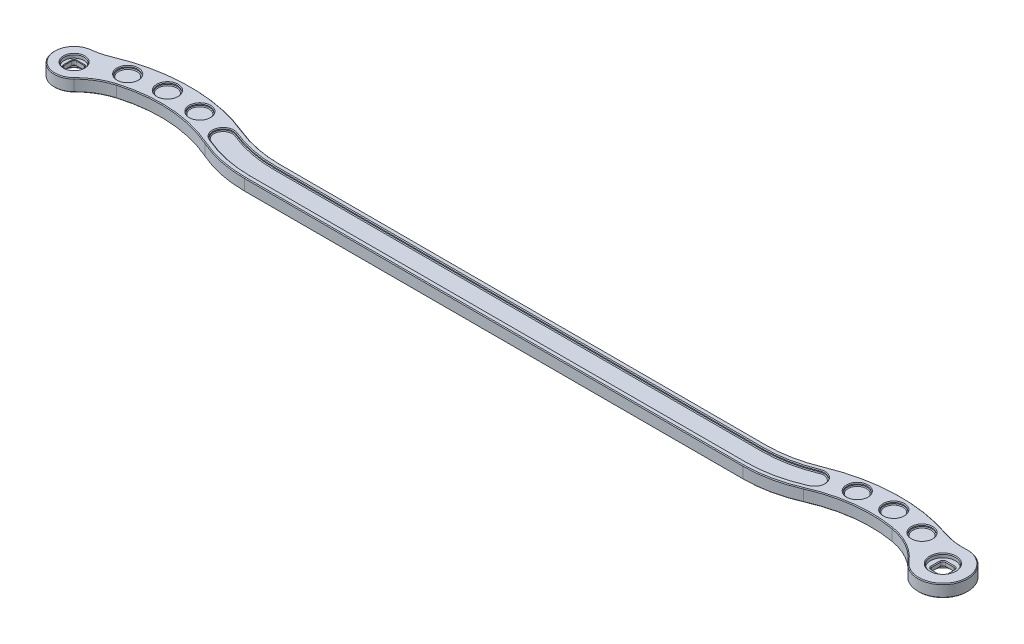
SolidWorks part; units mm, degrees
material "보통 탄소강"
ref_plane "정면" through (0, 0, 0) normal (0, 0, 1) x (1, 0, 0)
ref_plane "윗면" through (0, 0, 0) normal (0, 1, 0) x (1, 0, 0)
ref_plane "우측면" through (0, 0, 0) normal (1, 0, 0) x (0, 0, -1)
sketch "스케치1" plane through (0, 0, 0) normal (0, 1, 0) x (1, 0, 0)
  line L0 (0, 0) -> (350, 0) construction
  line L1 (77.0777, 6) -> (272.9223, 6)
  line L2 (74.6146, -6) -> (275.3854, -6)
  line L3 (335, 6.5992) -> (318, -52.3889) construction
  line L4 (75.0349, -4) -> (274.9651, -4)
  line L5 (0, 0) -> (32, 0) construction
  line L6 (32, 3) -> (32, 15) construction
  line L7 (32, 3) -> (32, 9) construction
  line L8 (175, 6) -> (175, -6) construction
  line L9 (273.3234, 4) -> (76.6766, 4)
  line L10 (307.4208, 8.0816) -> (318, -52.3889) construction
  line L11 (321.2949, 8.9115) -> (318, -52.3889) construction
  line L12 (294.089, 4.1521) -> (318, -52.3889) construction
  line L14 (347.25, -2.75) -> (352.75, -2.75)
  line L15 (347.25, -2.75) -> (347.25, 2.75)
  line L16 (347.25, 2.75) -> (352.75, 2.75)
  line L17 (352.75, -2.75) -> (352.75, 2.75)
  line L18 (347.25, -2.75) -> (352.75, 2.75) construction
  line L19 (347.25, 2.75) -> (352.75, -2.75) construction
  line L20 (2.5, -2.5) -> (-2.5, -2.5)
  line L21 (2.5, -2.5) -> (2.5, 2.5)
  line L22 (2.5, 2.5) -> (-2.5, 2.5)
  line L23 (-2.5, -2.5) -> (-2.5, 2.5)
  line L24 (2.5, -2.5) -> (-2.5, 2.5) construction
  line L25 (2.5, 2.5) -> (-2.5, -2.5) construction
  circle A2 centre (0, 0) radius 8
  circle A3 centre (350, 0) radius 10
  circle A6 centre (350, 0) radius 5
  circle A9 centre (32, 0) radius 3
  arc A11 (72.1368, -5.9386) -> (-6.5409, -4.6061) centre (32, -52.3889) ccw
  arc A12 (54.3968, -1.7301) -> (16.393, 0.7557) centre (32, -52.3889) ccw
  arc A13 (57.8775, 9.8334) -> (5.8839, 9.7336) centre (32, -52.3889) ccw
  arc A14 (57.3175, 7.8999) -> (13.8923, 10.4428) centre (32, -52.3889) ccw
  arc A15 (54.9979, 0.1904) -> (16.1077, 2.7556) centre (32, -52.3889) ccw
  circle A16 centre (15, 6.5992) radius 4
  circle A17 centre (32, -52.3889) radius 67.3889 construction
  circle A18 centre (32, -52.3889) radius 65.3889 construction
  circle A19 centre (32, -52.3889) radius 57.3889 construction
  circle A20 centre (32, -52.3889) radius 55.3889 construction
  arc A21 (64, 0) -> (18.8776, 7.5811) centre (32, -52.3889) ccw
  arc A22 (77.0777, 6) -> (57.8775, 9.8334) centre (77.0777, 56) cw
  arc A23 (76.6766, 4) -> (57.3175, 7.8999) centre (76.6766, 54) cw
  arc A24 (54.3968, -1.7301) -> (74.6146, -6) centre (74.6146, 44) ccw
  arc A25 (75.0349, -4) -> (54.9979, 0.1904) centre (75.0349, 46) cw
  arc A27 (295.0021, 0.1904) -> (333.8923, 2.7556) centre (318, -52.3889) cw
  arc A28 (274.9651, -4) -> (295.0021, 0.1904) centre (274.9651, 46) ccw
  arc A29 (295.6032, -1.7301) -> (275.3854, -6) centre (275.3854, 44) cw
  arc A30 (272.9223, 6) -> (292.1225, 9.8334) centre (272.9223, 56) ccw
  arc A31 (273.3234, 4) -> (292.6825, 7.8999) centre (273.3234, 54) ccw
  circle A32 centre (335, 6.5992) radius 4
  arc A33 (292.6825, 7.8999) -> (336.1077, 10.4428) centre (318, -52.3889) cw
  arc A34 (292.1225, 9.8334) -> (339.9749, 11.3164) centre (318, -52.3889) cw
  arc A35 (295.6032, -1.7301) -> (327.3652, 2.2025) centre (318, -52.3889) cw
  arc A36 (339.9749, 11.3164) -> (349.4649, 9.9857) centre (348.1272, 34.9499) ccw
  arc A37 (342.3252, -6.4107) -> (327.3652, 2.2025) centre (323.1382, -22.4375) ccw
  circle A38 centre (321.2949, 8.9115) radius 4
  circle A39 centre (307.4208, 8.0816) radius 4
  circle A40 centre (294.089, 4.1521) radius 4.0002
  circle A42 centre (15, 6.5992) radius 4
  circle A43 centre (28.7051, 8.9115) radius 4
  circle A44 centre (42.5792, 8.0816) radius 4
  circle A45 centre (55.911, 4.1521) radius 4.0002
  arc A46 (-0.9224, 7.9467) -> (5.8839, 9.7336) centre (-3.8047, 32.7799) ccw
  arc A47 (16.393, 0.7557) -> (5.6818, -5.6318) centre (23.4373, -23.2313) ccw
  circle A48 centre (0, 0) radius 4
  point P53 (175, 0)
  point P54 (175, 0)
  dimension "D3" = 5.5
  dimension "D4" = 16
  dimension "D5" = 20
  dimension "D8" = 4
  dimension "D11" = 10
  dimension "D12" = 50
  dimension "D14" = 6
  dimension "D9" = 2
  dimension "D18" = 50
  dimension "D19" = 13
  dimension "D21" = 13
  dimension "D22" = 8
  dimension "D23" = 50
  dimension "D24" = 25
  dimension "D27" = 8
  dimension "D1" = 350
  dimension "D6" = 6
  dimension "D7" = 6
  dimension "D10" = 4
  dimension "D13" = 32
  dimension "D15" = 12
  dimension "D17" = 15
  dimension "D20" = 13
  dimension "D26" = 5
  dimension "D16" = 2
extrude "보스-돌출1" add sketch "스케치1" along normal mid plane 2 contours A6 | A11 A48 L23 L22 L21 | A11 A48 L21 L20 L23 region at (-2.0344, 0, -3.3307) region at (-2.8693, 0, 1.9794) region at (345.1414, 0, 0)
extrude "보스-돌출3" add sketch "스케치1<4>" along normal mid plane 5 contours L4 A25 A11 A24 L2 A3 L1 A22 A13 A2 A16 A14 A23 A37 | A11 A2 | A2 A11 | A11 A25 A15 A16 A2 A12 A24 | A3 A6 | A6 | A11 A43 A14 A16 | A15 A43 A11 A16 | A11 A44 A14 A43 | A15 A44 A11 A43 | A11 A45 A14 A44 | A15 A45 A11 A44 | A40 A27 A39 A33 | A39 A27 A38 A33 | A38 A27 A32 A33 region at (175, 0, -5.649) region at (3.6453, 0, -6.8996) region at (356.6847, 0, -7.0525) region at (2.1307, 0, 3.4883) region at (9.3758, 0, -3.9532) region at (21.4174, 0, -10.3344) region at (22.1641, 0, -5.9089) region at (35.7983, 0, -11.1074) region at (35.5303, 0, -6.6274) region at (49.9842, 0, -8.6256) region at (48.7156, 0, -4.3206) region at (300.6197, 0, -6.5764) region at (314.3292, 0, -8.9749) region at (328.2271, 0, -8.2279) region at (345.1414, 0, 0)
sketch "스케치1<4>" plane through (0, 0, 0) normal (0, 1, 0) x (1, 0, 0) same geometry as "스케치1"
extrude "보스-돌출2" add sketch "스케치1<3>" along normal mid plane 3 contours L0 A37 | L0 L4 A37 | A37 L0 | L0 A37 | L0 | L0 | A25 A11 A16 A15 | A11 A16 | A16 A11 | A32 | A43 A21 | A43 A21 | A44 A21 | A44 A21 | A45 A21 | A45 A21 | A40 | A39 | A38 region at (175, 0, -5.649) region at (14.5364, 0, -8.2077) region at (15.4766, 0, -4.9456) region at (28.6153, 0, -10.5831) region at (28.7975, 0, -7.1931) region at (42.8677, 0, -9.7305) region at (42.2826, 0, -6.3864) region at (62.0542, 0, 0.7851) region at (55.2406, 0, -2.5669) region at (176.8355, 0, -0.1502) region at (56.563, 0, -5.6939) region at (294.089, 0, -4.1521) region at (307.4208, 0, -8.0816) region at (321.2949, 0, -8.9115) region at (335, 0, -6.5992)
sketch "스케치1<3>" plane through (0, 0, 0) normal (0, 1, 0) x (1, 0, 0) same geometry as "스케치1"
extrude "컷-돌출1" cut sketch "스케치1<6>" against normal blind 1.5 from surface contours A6 region at (345.1414, 0, 0) starting at face at (0, 2.5, 4)
sketch "스케치1<6>" plane through (0, 0, 0) normal (0, 1, 0) x (1, 0, 0) same geometry as "스케치1"
extrude "컷-돌출2" cut sketch "스케치1<7>" along normal blind 1.5 from surface contours A6 region at (345.1414, 0, 0) starting at face at (0, -2.5, 4)
sketch "스케치1<7>" plane through (0, 0, 0) normal (0, 1, 0) x (1, 0, 0) same geometry as "스케치1"
chamfer "모따기1" distance 0.3 angle 45 42 edges at (335, 1.5, -2.5992) (321.2949, 1.5, -4.9115) (307.4208, 1.5, -4.0816) (295.3241, 1.5, -0.3301) (285.2003, 1.5, 2.9412) (297.7775, 1.5, -5.7003) (283.1274, 1.5, -4.9706) (175, 1.5, -4) (175, 1.5, 4) (64.7997, 1.5, 2.9412) (66.8726, 1.5, -4.9706) (54.6759, 1.5, -0.3301) (52.2225, 1.5, -5.7003) (42.5792, 1.5, -4.0816) (28.7051, 1.5, -4.9115) (15, 1.5, -2.5992) (15, -1.5, -2.5992) (28.7051, -1.5, -4.9115) (42.5792, -1.5, -4.0816) (285.2003, -2.5, 2.9412) (295.3241, -2.5, -0.3301) (175, -2.5, 4) (297.7775, -2.5, -5.7003) (64.7997, -2.5, 2.9412) (283.1274, -2.5, -4.9706) (54.6759, -2.5, -0.3301) (175, -2.5, -4) (52.2225, -2.5, -5.7003) (66.8726, -2.5, -4.9706) (52.2225, -1.5, -5.7003) (66.8726, -1.5, -4.9706) (54.6759, -1.5, -0.3301) (64.7997, -1.5, 2.9412) (175, -1.5, 4) (175, -1.5, -4) (285.2003, -1.5, 2.9412) (295.3241, -1.5, -0.3301) (283.1274, -1.5, -4.9706) (297.7775, -1.5, -5.7003) (307.4208, -1.5, -4.0816) (321.2949, -1.5, -4.9115) (335, -1.5, -2.5992)
chamfer "모따기4" distance 0.3 angle 45 54 edges at (307.4208, 2.5, -4.0816) (335, 2.5, -2.5992) (321.2949, 2.5, -4.9115) (285.2003, 2.5, 2.9412) (295.3241, 2.5, -0.3301) (297.7775, 2.5, -5.7003) (283.1274, 2.5, -4.9706) (175, 2.5, 4) (175, 2.5, -4) (64.7997, 2.5, 2.9412) (54.6759, 2.5, -0.3301) (66.8726, 2.5, -4.9706) (52.2225, 2.5, -5.7003) (42.5792, 2.5, -4.0816) (28.7051, 2.5, -4.9115) (15, 2.5, -2.5992) (15, -2.5, -2.5992) (28.7051, -2.5, -4.9115) (42.5792, -2.5, -4.0816) (307.4208, -2.5, -4.0816) (321.2949, -2.5, -4.9115) (335, -2.5, -2.5992) (335.6122, -2.5, 0.7719) (311.194, -2.5, -2.5803) (285.7173, -2.5, 4.9209) (175, -2.5, 6) (64.2827, -2.5, 4.9209) (35.6153, -2.5, -2.8819) (-7.1942, -2.5, 3.499) (31.8707, -2.5, -14.9999) (67.2882, -2.5, -6.9677) (175, -2.5, -6) (282.7118, -2.5, -6.9677) (315.9126, -2.5, -14.9677) (344.6556, -2.5, -10.1921) (359.1685, -2.5, 3.9924) (359.1685, 2.5, 3.9924) (335.6122, 2.5, 0.7719) (344.6556, 2.5, -10.1921) (311.194, 2.5, -2.5803) (315.9126, 2.5, -14.9677) (285.7173, 2.5, 4.9209) (282.7118, 2.5, -6.9677) (175, 2.5, -6) (175, 2.5, 6) (64.2827, 2.5, 4.9209) (67.2882, 2.5, -6.9677) (35.6153, 2.5, -2.8819) (31.8707, 2.5, -14.9999) (-7.1942, 2.5, 3.499) (10.6327, -2.5, 1.7594) (2.5439, -2.5, -8.5995) (2.5439, 2.5, -8.5995) (10.6327, 2.5, 1.7594)
fillet "필렛1" radius 1 8 edges at (347.25, 0, -2.75) (347.25, 0, 2.75) (352.75, 0, 2.75) (352.75, 0, -2.75) (-2.5, 0, 2.5) (2.5, 0, 2.5) (2.5, 0, -2.5) (-2.5, 0, -2.5)
chamfer "모따기5" distance 0.3 angle 45 19 edges at (350, 2.5, 5) (350, -1, 2.75) (347.25, -1, 0) (352.75, -1, 0) (350, -1, -2.75) (350, 1, 2.75) (352.75, 1, 0) (347.25, 1, 0) (350, 1, -2.75) (0, 2.5, 4) (0, -2.5, 4) (347.5429, -1, 2.4571) (352.4571, -1, 2.4571) (347.5429, -1, -2.4571) (352.4571, -1, -2.4571) (352.4571, 1, 2.4571) (347.5429, 1, 2.4571) (352.4571, 1, -2.4571) (347.5429, 1, -2.4571)
chamfer "모따기6" distance 0.2 angle 45 16 edges at (0, -1, 2.5) (-2.5, -1, 0) (2.5, -1, 0) (0, -1, -2.5) (0, 1, 2.5) (2.5, 1, 0) (-2.5, 1, 0) (0, 1, -2.5) (2.2071, -1, 2.2071) (-2.2071, -1, 2.2071) (2.2071, -1, -2.2071) (-2.2071, -1, -2.2071) (2.2071, 1, 2.2071) (-2.2071, 1, 2.2071) (2.2071, 1, -2.2071) (-2.2071, 1, -2.2071)
